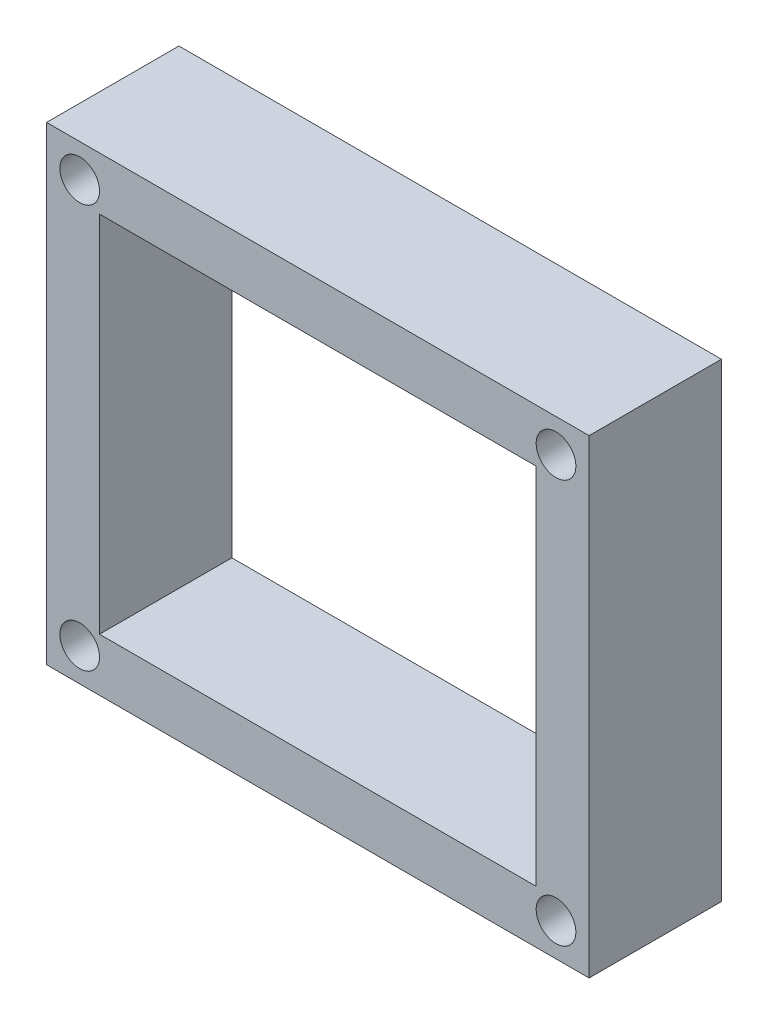
SolidWorks part; units mm, degrees
note: The reader was unsure of these and kept them because the rebuilt part matched: shared geometry of "草图1<3>".
ref_plane "前视基准面" through (0, 0, 0) normal (0, 0, 1) x (1, 0, 0)
ref_plane "上视基准面" through (0, 0, 0) normal (0, 1, 0) x (1, 0, 0)
ref_plane "右视基准面" through (0, 0, 0) normal (1, 0, 0) x (0, 0, -1)
sketch "草图1" plane through (0, 0, 0) normal (0, 0, 1) x (1, 0, 0)
  line L0 (-41, 35.5) -> (-41, -35.5)
  line L1 (-33, 27.5) -> (33, 27.5)
  line L2 (-33, 27.5) -> (-33, -27.5)
  line L3 (-33, -27.5) -> (33, -27.5)
  line L4 (33, 27.5) -> (33, -27.5)
  line L5 (-33, 27.5) -> (33, -27.5) construction
  line L6 (-33, -27.5) -> (33, 27.5) construction
  line L7 (-41, -35.5) -> (41, -35.5)
  line L8 (41, 35.5) -> (41, -35.5)
  line L9 (-41, 35.5) -> (41, 35.5)
  line L10 (33, 27.5) -> (41, 35.5) construction
  line L11 (33, -27.5) -> (41, -35.5) construction
  line L12 (-33, -27.5) -> (-41, -35.5) construction
  line L13 (-33, 27.5) -> (-41, 35.5) construction
  circle A4 centre (36, -30.5) radius 3
  circle A5 centre (36, 30.5) radius 3
  circle A6 centre (-36, 30.5) radius 3
  circle A7 centre (-36, -30.5) radius 3
  point P0 (0, 0)
  dimension "D1" = 8
extrude "凸台-拉伸1" add sketch "草图1" along normal blind 20
extrude "切除-拉伸1" cut sketch "草图1<3>" along normal blind 20
sketch "草图1<3>" plane through (0, 0, 0) normal (0, 0, 1) x (1, 0, 0) same geometry as "草图1"
